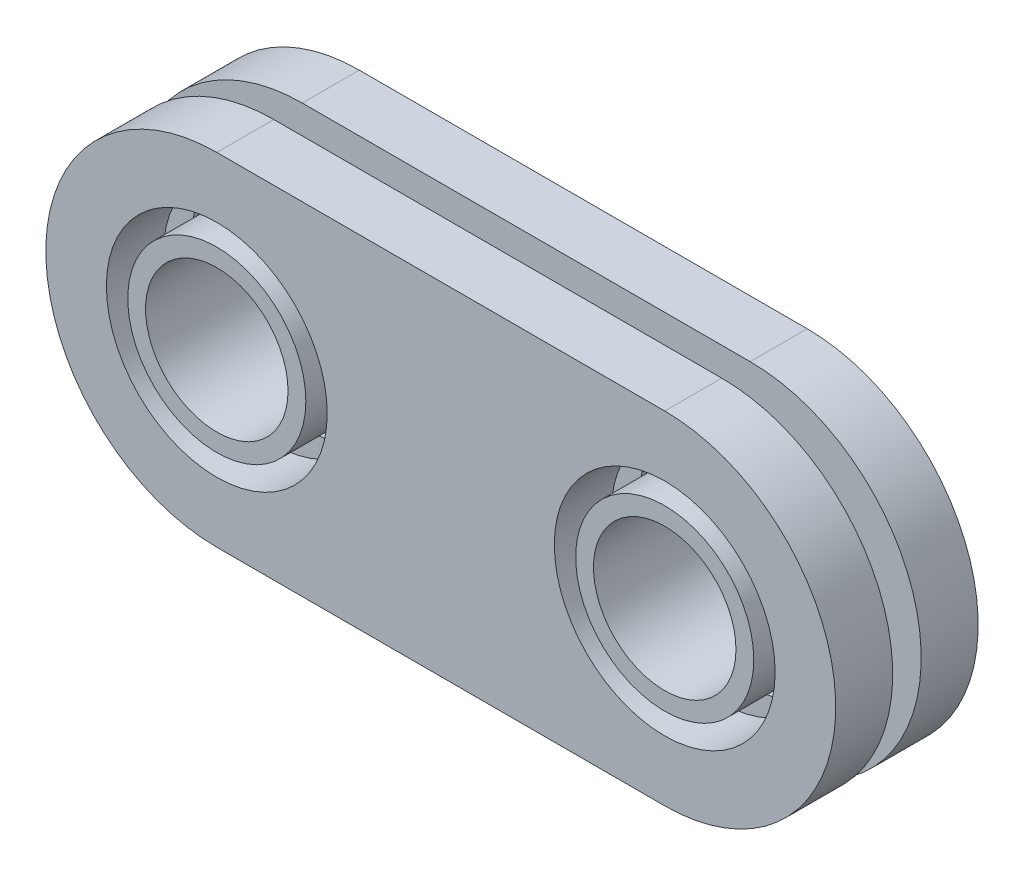
SolidWorks part; units mm, degrees
note: '?' marks a value the reader was unsure of.
material "Plain Carbon Steel"
ref_plane "Front Plane" through (0, 0, 0) normal (0, 0, 1) x (1, 0, 0)
ref_plane "Top Plane" through (0, 0, 0) normal (0, 1, 0) x (1, 0, 0)
ref_plane "Right Plane" through (0, 0, 0) normal (1, 0, 0) x (0, 0, -1)
ref_plane "Plane1" through (6.2876, 0, 0) normal (1, 0, 0) x (0, 0, -1)
sketch "Sketch1" plane through (0, 0, 0) normal (0, 0, 1) x (1, 0, 0)
  line L0 (0, -2.4) -> (6.2876, -2.4)
  line L1 (6.2876, 2.4) -> (0, 2.4)
  arc A0 (6.2876, -2.4) -> (6.2876, 2.4) centre (6.2876, 0) ccw
  arc A1 (0, 2.4) -> (0, -2.4) centre (0, 0) ccw
  circle A2 centre (0, 0) radius 1.55
  circle A3 centre (6.2876, 0) radius 1.55
  dimension "D2" = 2.4
  dimension "D3" = 2.4
  dimension "D4" = 3.1
  dimension "D6" = 3.1
  dimension "D1" = 6.2876
  dimension "D5" = 6.2876
extrude "Boss-Extrude1" add sketch "Sketch1" along normal blind 0.8 from offset 0.2
sketch "Sketch2" plane through (0, 0, 0) normal (0, 0, 1) x (1, 0, 0)
  line L0 (0, -2.4) -> (6.2876, -2.4)
  line L1 (6.2876, 2.4) -> (0, 2.4)
  arc A0 (6.2876, -2.4) -> (6.2876, 2.4) centre (6.2876, 0) ccw
  arc A1 (0, 2.4) -> (0, -2.4) centre (0, 0) ccw
  circle A2 centre (0, 0) radius 1.55
  circle A3 centre (6.2876, 0) radius 1.55
  dimension "D2" = 2.4
  dimension "D3" = 2.4
  dimension "D4" = 3.1
  dimension "D6" = 3.1
  dimension "D1" = 6.2876
  dimension "D5" = 6.2876
extrude "Boss-Extrude2" add sketch "Sketch2" along normal blind 0.8 from offset 1
sketch "Sketch3" plane through (0, 0, 0) normal (0, 0, 1) x (1, 0, 0)
  circle A0 centre (0, 0) radius 1.25
  circle A1 centre (0, 0) radius 1
  circle A2 centre (6.2876, 0) radius 1.25
  circle A3 centre (6.2876, 0) radius 1
  dimension "D1" = 2.5
  dimension "D2" = 2
  dimension "D4" = 2.5
  dimension "D6" = 2
  dimension "D3" = 6.2876
  dimension "D5" = 6.2876
extrude "Boss-Extrude3" add sketch "Sketch3" along normal blind 2 from offset 1
ref_axis "Axis1" through (0, 0, -1.1) along (0, 0, 1)?
ref_axis "Axis2" through (6.2876, 0, -1.1) along (0, 0, 1)?
